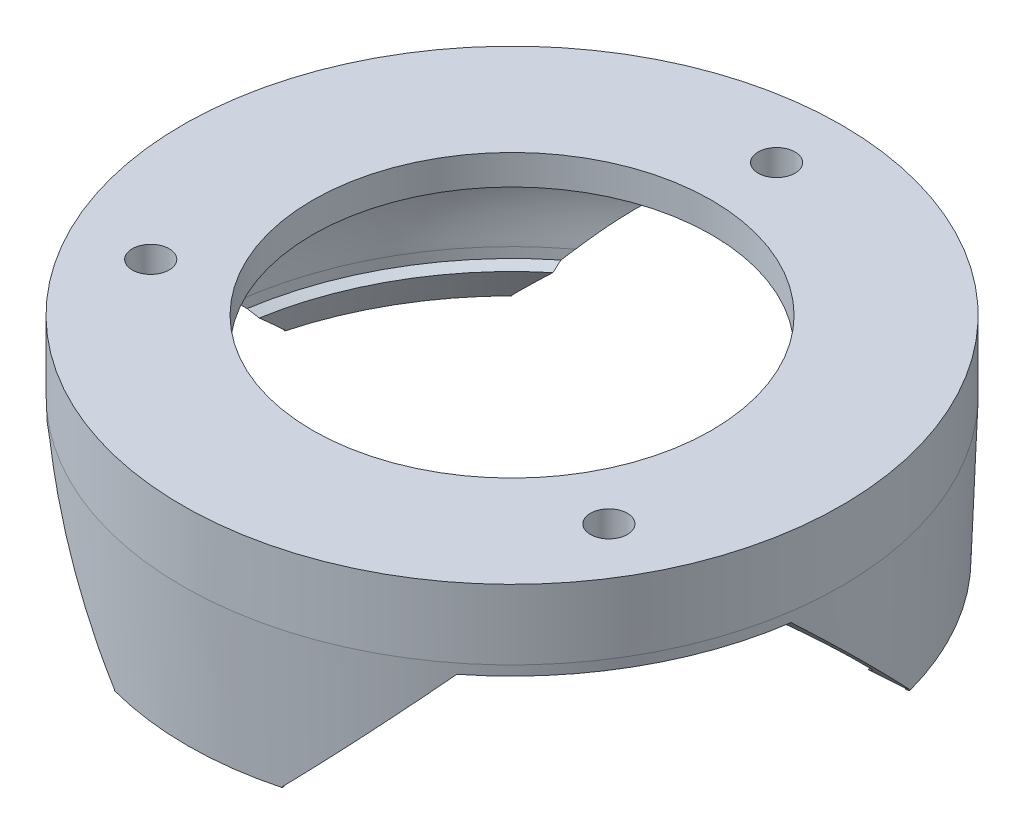
SolidWorks part; units mm, degrees
ref_plane "Front Plane" through (0, 0, 0) normal (0, 0, 1) x (1, 0, 0)
ref_plane "Top Plane" through (0, 0, 0) normal (0, 1, 0) x (1, 0, 0)
ref_plane "Right Plane" through (0, 0, 0) normal (1, 0, 0) x (0, 0, -1)
sketch "Sketch1" plane through (0, 0, 0) normal (0, 0, 1) x (1, 0, 0)
  line L1 (21.9764, -3) -> (20, -3)
  line L2 (0, 0) -> (0, 30.0917) construction
  line L4 (31.775, -16.5053) -> (31.775, -17.5398)
  line L5 (31.775, -17.5398) -> (30.975, -18.1)
  line L6 (30.975, -18.1) -> (32.225, -21.1)
  line L10 (33.05, -7) -> (33.05, 0)
  line L11 (33.05, 0) -> (20, 0)
  line L12 (20, 0) -> (20, -3)
  line L13 (32.225, -21.1) -> (32.55, -21.1)
  line L14 (32.55, -21.1) -> (33.05, -7)
  line L15 (21.9764, -3) -> (31.775, -16.5053) construction
  line L16 (26.8757, -9.7527) -> (30.1235, -7.3963) construction
  spline S0 degree 3 poles (21.9764, -3) (24.1294, -3) (32.2948, -5.7059) (31.775, -15.1732) (31.775, -16.5053) knots 0 0 0 0 0.5 1 1 1 1
  dimension "D8" = 0.5
  dimension "D1" = 40
  dimension "D2" = 18.1
  dimension "D3" = 3
  dimension "D4" = 66.1
  dimension "D5" = 61.95
  dimension "D6" = 7
  dimension "D7" = 125
  dimension "D9" = 3
  dimension "D10" = 0.8
  dimension "D11" = 1.25
revolve "Revolve1" add sketch "Sketch1" angle 360 about L2
sketch "Sketch2" plane through (0, 0, 0) normal (0, 1, 0) x (1, 0, 0)
  line L4 (-23.3699, 23.3699) -> (-14.1421, 14.1421)
  line L5 (14.1421, 14.1421) -> (23.3699, 23.3699)
  line L22 (31.9238, 8.554) -> (19.3185, 5.1764)
  line L23 (5.1764, -19.3185) -> (8.554, -31.9238)
  line L24 (-8.554, -31.9238) -> (-5.1764, -19.3185)
  line L25 (-19.3185, 5.1764) -> (-31.9238, 8.554)
  arc A0 (14.1421, 14.1421) -> (-14.1421, 14.1421) centre (0, 0) ccw
  arc A1 (23.3699, 23.3699) -> (-23.3699, 23.3699) centre (0, 0) ccw
  circle A2 centre (0, 0) radius 33.05 construction
  circle A3 centre (0, 0) radius 20 construction
  arc A4 (5.1764, -19.3185) -> (19.3185, 5.1764) centre (0, 0) ccw
  arc A5 (8.554, -31.9238) -> (31.9238, 8.554) centre (0, 0) ccw
  arc A6 (-19.3185, 5.1764) -> (-5.1764, -19.3185) centre (0, 0) ccw
  arc A7 (-31.9238, 8.554) -> (-8.554, -31.9238) centre (0, 0) ccw
  point P1 (0, 33.05)
  dimension "D1" = 90
extrude "Cut-Extrude1" cut sketch "Sketch2" against normal through all from offset 8 offset against normal yes
sketch "Sketch3" plane through (0, 0, 0) normal (0, 1, 0) x (1, 0, 0)
  line L1 (0, 20) -> (0, 33.05) construction
  circle A0 centre (0, 26.525) radius 1.85
  circle A2 centre (0, 0) radius 20 construction
  circle A3 centre (0, 0) radius 33.05 construction
  circle A4 centre (22.9713, -13.2625) radius 1.85
  circle A5 centre (-22.9713, -13.2625) radius 1.85
  point P4 (0, 26.525)
  point P18 (0, 0)
  dimension "D1" = 3.7
  dimension "D2" = 3
extrude "Cut-Extrude3" cut sketch "Sketch3" against normal blind 10
chamfer "Chamfer1" distance 13 angle 45 6 edges at (-30.658, -8, -8.2148) (-22.4432, -8, -22.4432) (22.4432, -8, -22.4432) (8.2148, -8, 30.658) (30.658, -8, -8.2148) (-8.2148, -8, 30.658)
